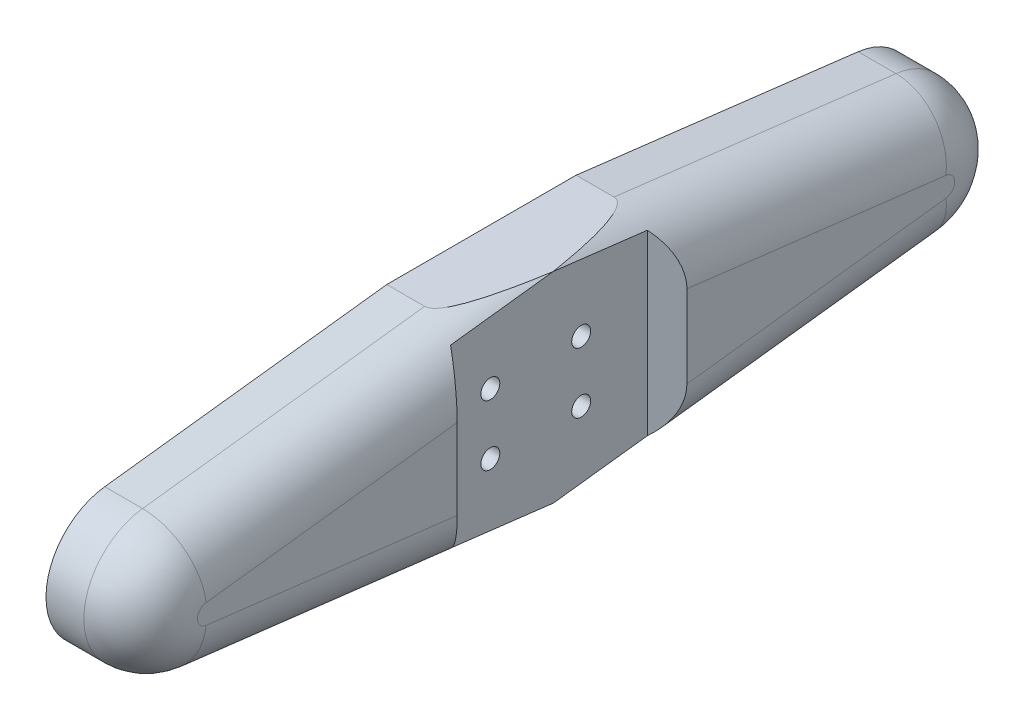
SolidWorks part; units mm, degrees
ref_plane "Спереди XY" through (0, 0, 0) normal (0, 0, 1) x (1, 0, 0)
ref_plane "Сверху XZ" through (0, 0, 0) normal (0, 1, 0) x (1, 0, 0)
ref_plane "Справа ZY" through (0, 0, 0) normal (1, 0, 0) x (0, 0, -1)
sketch "Эскиз4" plane through (0, 0, 0) normal (1, 0, 0) x (0, 0, -1)
  line L0 (-25, 26.5) -> (25, 26.5)
  line L1 (25, 26.5) -> (99.4872, 17.5)
  line L2 (99.4872, -17.5) -> (25, -26.5)
  line L3 (25, -26.5) -> (-25, -26.5)
  line L4 (-25, -26.5) -> (-99.4872, -17.5)
  line L5 (-99.4872, 17.5) -> (-25, 26.5)
  line L6 (25, -26.5) -> (-25, 26.5) construction
  line L7 (25, 26.5) -> (-25, -26.5) construction
  arc A4 (99.4872, 17.5) -> (99.4872, -17.5) centre (97.3727, 0) cw
  arc A5 (-99.4872, 17.5) -> (-99.4872, -17.5) centre (-97.3727, 0) ccw
  point P10 (0, 26.5)
  point P11 (-115, 0)
  point P12 (115, 0)
  dimension "D1" = 50
  dimension "D2" = 230
  dimension "D3" = 53
  dimension "D6" = 35
  dimension "D7" = 35
extrude "Бобышка-Вытянуть1" add sketch "Эскиз4" along normal blind 25 contours L5 L0 L1 A4 L2 L3 L4 A5
fillet "Скругление2" radius 15 6 edges at (25, 22, -62.2436) (25, 0, -115) (25, 22, 62.2436) (25, -22, 62.2436) (25, -22, -62.2436) (25, 0, 115)
sketch "Эскиз8" plane through (0, 0, 0) normal (0, 1, 0) x (1, 0, 0)
  line L0 (19, -27.1528) -> (19, 24.8472)
  line L1 (19, 24.8472) -> (28, 31.4746)
  line L2 (28, 31.4746) -> (28, -33.5254)
  line L3 (28, -33.5254) -> (19, -27.1528)
  line L5 (25, 0) -> (25, 97.6879) construction
  point P2 (0, 0)
  point P7 (28, -33.5254)
  dimension "D1" = 52
  dimension "D2" = 65
  dimension "D3" = 9
  dimension "D4" = 6
extrude "Вырез-Вытянуть2" cut sketch "Эскиз8" against normal through all both and the other way through all
sketch "Эскиз9" plane through (19, 0, 0) normal (1, 0, 0) x (0, 0, -1)
  line L0 (-27.1528, -23.2181) -> (-27.1528, 23.2181) construction
  circle A0 centre (-16.6528, 8) radius 2.5
  circle A1 centre (-16.6528, -8) radius 2.5
  point P4 (0, 0)
  point P5 (0, 0)
  point P8 (-16.6528, 8.2008)
  dimension "D1" = 5
  dimension "D4" = 5
  dimension "D2" = 10.5
  dimension "D3" = 18.5
  dimension "D5" = 16
extrude "Вырез-Вытянуть3" cut sketch "Эскиз9" against normal through all
pattern_linear "Линейный массив1" count 2 spacing 24 along (0, 0, -1) of "Вырез-Вытянуть3"
sketch "Эскиз10" plane through (0, 0, 0) normal (-1, 0, 0) x (0, 0, 1)
  line L36 (99.0074, 13.5289) -> (24.7592, 22.5)
  line L37 (24.7592, 22.5) -> (-24.7592, 22.5)
  line L38 (-24.7592, 22.5) -> (-99.0074, 13.5289)
  line L39 (-99.0074, -13.5289) -> (-24.7592, -22.5)
  line L40 (-24.7592, -22.5) -> (24.7592, -22.5)
  line L41 (24.7592, -22.5) -> (99.0074, -13.5289)
  line L42 (99.0074, 13.5289) -> (24.7592, 22.5)
  line L43 (24.7592, 22.5) -> (-24.7592, 22.5)
  line L44 (-24.7592, 22.5) -> (-99.0074, 13.5289)
  line L45 (-99.0074, -13.5289) -> (-24.7592, -22.5)
  line L46 (-24.7592, -22.5) -> (24.7592, -22.5)
  line L47 (24.7592, -22.5) -> (99.0074, -13.5289)
  arc A8 (99.0074, -13.5289) -> (99.0074, 13.5289) centre (97.3727, 0) ccw
  arc A9 (-99.0074, 13.5289) -> (-99.0074, -13.5289) centre (-97.3727, 0) ccw
  arc A10 (99.0074, -13.5289) -> (99.0074, 13.5289) centre (97.3727, 0) ccw
  arc A11 (-99.0074, 13.5289) -> (-99.0074, -13.5289) centre (-97.3727, 0) ccw
  dimension "D1" = 4
extrude "Вырез-Вытянуть4" cut sketch "Эскиз10" against normal blind 14
sketch "Эскиз11" plane through (14, 0, 0) normal (-1, 0, 0) x (0, 0, 1)
  circle A0 centre (97.5529, 0) radius 7.5
  circle A1 centre (97.5529, 0) radius 3.25
  dimension "D1" = 15
  dimension "D2" = 6.5
extrude "Бобышка-Вытянуть3" add sketch "Эскиз11" along normal blind 14
pattern_linear "Линейный массив2" count 2 spacing 195 along (0, 0, -1) of "Бобышка-Вытянуть3"
